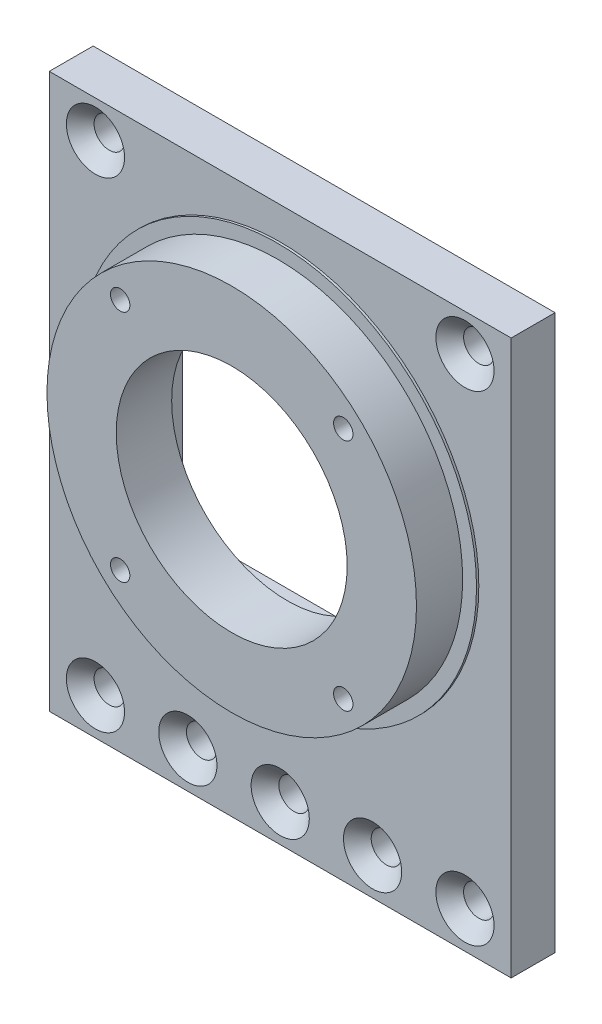
SolidWorks part; units mm, degrees
material "PVC rigide"
ref_plane "Plan de face" through (0, 0, 0) normal (0, 0, 1) x (1, 0, 0)
ref_plane "Plan de dessus" through (0, 0, 0) normal (0, 1, 0) x (1, 0, 0)
ref_plane "Plan de droite" through (0, 0, 0) normal (1, 0, 0) x (0, 0, -1)
sketch "Esquisse1" plane through (0, 0, 0) normal (0, 0, 1) x (1, 0, 0)
  line L1 (28, 28) -> (-28, 28)
  line L2 (28, 28) -> (28, -28)
  line L3 (28, -28) -> (-28, -28)
  line L4 (-28, 28) -> (-28, -28)
  line L5 (28, 28) -> (-28, -28) construction
  line L6 (28, -28) -> (-28, 28) construction
  line L7 (50, 50) -> (-50, 50)
  line L8 (50, 50) -> (50, -50)
  line L9 (50, -50) -> (-50, -50)
  line L10 (-50, 50) -> (-50, -50)
  line L11 (50, 50) -> (-50, -50) construction
  line L12 (50, -50) -> (-50, 50) construction
  circle A0 centre (0, 0) radius 40 construction
  point P0 (0, 0)
  dimension "D2" = 80
  dimension "D1" = 56
  dimension "D3" = 100
extrude "Boss.-Extru.1" add sketch "Esquisse1" along normal blind 10
fillet "Congé1" radius 3.5 4 edges at (-28, -28, 5) (28, 28, 5) (-28, 28, 5) (28, -28, 5)
sketch "Esquisse3" plane through (0, 0, 10) normal (0, 0, 1) x (1, 0, 0)
  line L5 (-28, 24.5) -> (-28, -24.5)
  line L6 (24.5, 28) -> (-24.5, 28)
  line L7 (28, -24.5) -> (28, 24.5)
  line L8 (-24.5, -28) -> (24.5, -28)
  line L9 (-28, 24.5) -> (-28, -24.5)
  line L10 (24.5, 28) -> (-24.5, 28)
  line L11 (28, -24.5) -> (28, 24.5)
  line L12 (-24.5, -28) -> (24.5, -28)
  circle A0 centre (0, 0) radius 40
  arc A5 (-24.5, 28) -> (-28, 24.5) centre (-24.5, 24.5) ccw
  arc A6 (28, 24.5) -> (24.5, 28) centre (24.5, 24.5) ccw
  arc A7 (24.5, -28) -> (28, -24.5) centre (24.5, -24.5) ccw
  arc A8 (-28, -24.5) -> (-24.5, -28) centre (-24.5, -24.5) ccw
  arc A9 (-24.5, 28) -> (-28, 24.5) centre (-24.5, 24.5) ccw
  arc A10 (28, 24.5) -> (24.5, 28) centre (24.5, 24.5) ccw
  arc A11 (24.5, -28) -> (28, -24.5) centre (24.5, -24.5) ccw
  arc A12 (-28, -24.5) -> (-24.5, -28) centre (-24.5, -24.5) ccw
  dimension "D1" = 80
  dimension "D2" = 0
extrude "Boss.-Extru.2" add sketch "Esquisse3" along normal blind 10
sketch "Esquisse4" plane through (0, 0, 10) normal (0, 0, 1) x (1, 0, 0)
  circle A0 centre (0, 0) radius 43
  circle A1 centre (0, 0) radius 40 construction
  dimension "D1" = 3
extrude "Enlèv. mat.-Extru.2" cut sketch "Esquisse4" against normal blind 0.5 flip side to cut
sketch "Esquisse5" plane through (0, 0, 0) normal (0, 0, -1) x (-1, 0, 0)
  line L1 (30.7, -30.7) -> (-30.7, -30.7)
  line L2 (30.7, -30.7) -> (30.7, 30.7)
  line L3 (30.7, 30.7) -> (-30.7, 30.7)
  line L4 (-30.7, -30.7) -> (-30.7, 30.7)
  line L5 (30.7, -30.7) -> (-30.7, 30.7) construction
  line L6 (30.7, 30.7) -> (-30.7, -30.7) construction
  point P0 (0, 0)
  dimension "D1" = 61.4
extrude "Enlèv. mat.-Extru.3" cut sketch "Esquisse5" against normal blind 9
sketch "Esquisse6" plane through (0, 0, 9) normal (0, 0, -1) x (-1, 0, 0)
  line L4 (-30.7, 30.7) -> (-30.7, -30.7)
  line L5 (-30.7, -30.7) -> (30.7, -30.7)
  line L6 (30.7, -30.7) -> (30.7, 30.7)
  line L7 (30.7, 30.7) -> (-30.7, 30.7)
  line L8 (-30.7, 30.7) -> (-30.7, -30.7)
  line L9 (-30.7, -30.7) -> (30.7, -30.7)
  line L10 (30.7, -30.7) -> (30.7, 30.7)
  line L11 (30.7, 30.7) -> (-30.7, 30.7)
  line L13 (28, -24.5) -> (28, 24.5)
  line L14 (-24.5, -28) -> (24.5, -28)
  line L15 (-28, 24.5) -> (-28, -24.5)
  line L16 (24.5, 28) -> (-24.5, 28)
  line L17 (28, -24.5) -> (28, 24.5)
  line L18 (-24.5, -28) -> (24.5, -28)
  line L19 (-28, 24.5) -> (-28, -24.5)
  line L20 (24.5, 28) -> (-24.5, 28)
  arc A4 (28, 24.5) -> (24.5, 28) centre (24.5, 24.5) ccw
  arc A5 (24.5, -28) -> (28, -24.5) centre (24.5, -24.5) ccw
  arc A6 (-28, -24.5) -> (-24.5, -28) centre (-24.5, -24.5) ccw
  arc A7 (-24.5, 28) -> (-28, 24.5) centre (-24.5, 24.5) ccw
  arc A8 (28, 24.5) -> (24.5, 28) centre (24.5, 24.5) ccw
  arc A9 (24.5, -28) -> (28, -24.5) centre (24.5, -24.5) ccw
  arc A10 (-28, -24.5) -> (-24.5, -28) centre (-24.5, -24.5) ccw
  arc A11 (-24.5, 28) -> (-28, 24.5) centre (-24.5, 24.5) ccw
  dimension "D1" = 0
  dimension "D2" = 0
extrude "Boss.-Extru.3" add sketch "Esquisse6" along normal blind 1
sketch "Esquisse12" plane through (0, -50, 0) normal (0, -1, 0) x (1, 0, 0)
  line L4 (50, 9.5) -> (-50, 9.5)
  line L5 (-50, 9.5) -> (-50, 0)
  line L6 (-50, 0) -> (50, 0)
  line L7 (50, 0) -> (50, 9.5)
  line L8 (50, 9.5) -> (-50, 9.5)
  line L9 (-50, 9.5) -> (-50, 0)
  line L10 (-50, 0) -> (50, 0)
  line L11 (50, 0) -> (50, 9.5)
  dimension "D1" = 0
extrude "Boss.-Extru.5" add sketch "Esquisse12" along normal blind 20
sketch "Esquisse7" plane through (0, 0, 8) normal (0, 0, -1) x (-1, 0, 0)
  line L5 (-24.5, -28) -> (24.5, -28)
  line L6 (28, -24.5) -> (28, 24.5)
  line L7 (24.5, 28) -> (-24.5, 28)
  line L8 (-28, 24.5) -> (-28, -24.5)
  line L9 (-24.5, -28) -> (24.5, -28)
  line L10 (28, -24.5) -> (28, 24.5)
  line L11 (24.5, 28) -> (-24.5, 28)
  line L12 (-28, 24.5) -> (-28, -24.5)
  circle A0 centre (0, 0) radius 25
  arc A5 (24.5, -28) -> (28, -24.5) centre (24.5, -24.5) ccw
  arc A6 (28, 24.5) -> (24.5, 28) centre (24.5, 24.5) ccw
  arc A7 (-24.5, 28) -> (-28, 24.5) centre (-24.5, 24.5) ccw
  arc A8 (-28, -24.5) -> (-24.5, -28) centre (-24.5, -24.5) ccw
  arc A9 (24.5, -28) -> (28, -24.5) centre (24.5, -24.5) ccw
  arc A10 (28, 24.5) -> (24.5, 28) centre (24.5, 24.5) ccw
  arc A11 (-24.5, 28) -> (-28, 24.5) centre (-24.5, 24.5) ccw
  arc A12 (-28, -24.5) -> (-24.5, -28) centre (-24.5, -24.5) ccw
  dimension "D1" = 50
  dimension "D2" = 0
extrude "Boss.-Extru.4" add sketch "Esquisse7" against normal up to surface (12 mm away) up to face at (40, 0, 20)
sketch "Esquisse10" plane through (0, 0, 8) normal (0, 0, -1) x (-1, 0, 0)
  line L1 (-24.1504, -25.3329) -> (24.1504, -25.3329) construction
  line L2 (-24.1504, -25.3329) -> (-24.1504, 25.3329) construction
  line L3 (-24.1504, 25.3329) -> (24.1504, 25.3329) construction
  line L4 (24.1504, -25.3329) -> (24.1504, 25.3329) construction
  line L5 (-24.1504, -25.3329) -> (24.1504, 25.3329) construction
  line L6 (-24.1504, 25.3329) -> (24.1504, -25.3329) construction
  circle A0 centre (0, 0) radius 35 construction
  point P0 (0, 0)
  dimension "D1" = 70
hole_wizard "Trou taraudé M5x0.81" positions "Esquisse3D2" profile "Esquisse11" tap size "M5x0.8" standard "Ansi Metric" end condition through all
sketch3d "Esquisse3D2"
  point P0 (24.1504, 25.3329, 8)
  point P3 (24.1504, -25.3329, 8)
  point P6 (-24.1504, 25.3329, 8)
  point P9 (-24.1504, -25.3329, 8)
sketch "Esquisse11" plane through (24.1504, 25.3329, 8) normal (1, 0, 0) x (0, 1, 0)
  line L0 (0, 0) -> (0, 12)
  line L1 (0, 12) -> (2.1, 12)
  line L2 (2.1, 12) -> (2.1, 0)
  line L5 (2.1, 0) -> (0, 0)
  line L11 (0, -6.35) -> (0, 107.95) construction
  dimension "Diamètre principal du filetage" = 4.2
  dimension "Profondeur du trou pour taraudage jusqu'au prochain" = 12
sketch "Esquisse13" plane through (0, 0, 9.5) normal (0, 0, 1) x (1, 0, 0)
  line L0 (-50, -62) -> (50, -62) construction
  line L1 (-50, 50) -> (-50, -70) construction
  line L2 (50, -70) -> (50, 50) construction
  line L3 (50, -70) -> (-50, -70) construction
  line L4 (0, -62) -> (0, -70) construction
  line L5 (-40, -62) -> (-40, -70) construction
  line L6 (40, -62) -> (40, -70) construction
  line L7 (-20, -62) -> (-20, -70) construction
  line L8 (20, -62) -> (20, -70) construction
  line L9 (-50, 42) -> (50, 42) construction
  line L10 (50, 50) -> (-50, 50) construction
  line L11 (-40, -62) -> (-40, 50) construction
  line L12 (40, -62) -> (40, 50) construction
  dimension "D1" = 8
  dimension "D2" = 10
  dimension "D3" = 20
  dimension "D4" = 8
hole_wizard "Fraisage pour vis à tête fraisée M61" positions "Esquisse3D3" profile "Esquisse14" countersink size "M6" standard "Ansi Metric" end condition through all
sketch3d "Esquisse3D3"
  line L0 (-40, -62, 9.5) -> (-40, -70, 9.5) construction
  line L1 (-50, 42, 9.5) -> (50, 42, 9.5) construction
  line L2 (40, -62, 9.5) -> (40, 50, 9.5) construction
  line L3 (-40, -62, 9.5) -> (-40, 50, 9.5) construction
  point P0 (-40, -62, 9.5)
  point P4 (-20, -62, 9.5)
  point P7 (0, -62, 9.5)
  point P10 (20, -62, 9.5)
  point P13 (40, -62, 9.5)
  point P21 (-40, 42, 9.5)
  point P25 (40, 42, 9.5)
sketch "Esquisse14" plane through (-40, -62, 9.5) normal (1, 0, 0) x (0, -1, 0)
  line L0 (0, 0) -> (0, 9.5)
  line L1 (0, 9.5) -> (3.3, 9.5)
  line L2 (3.3, 9.5) -> (3.3, 3)
  line L3 (3.3, 3) -> (6.3, 0)
  line L5 (6.3, 0) -> (0, 0)
  line L6 (-3.3, 3) -> (-6.3, 0) construction
  line L11 (0, -6.35) -> (0, 107.95) construction
  dimension "Diamètre du perçage jusqu'au prochain" = 6.6
  dimension "Profondeur du perçage jusqu'au prochain" = 9.5
  dimension "Diamètre du fraisage entrant" = 12.6
  dimension "Angle du fraisage entrant" = 90
